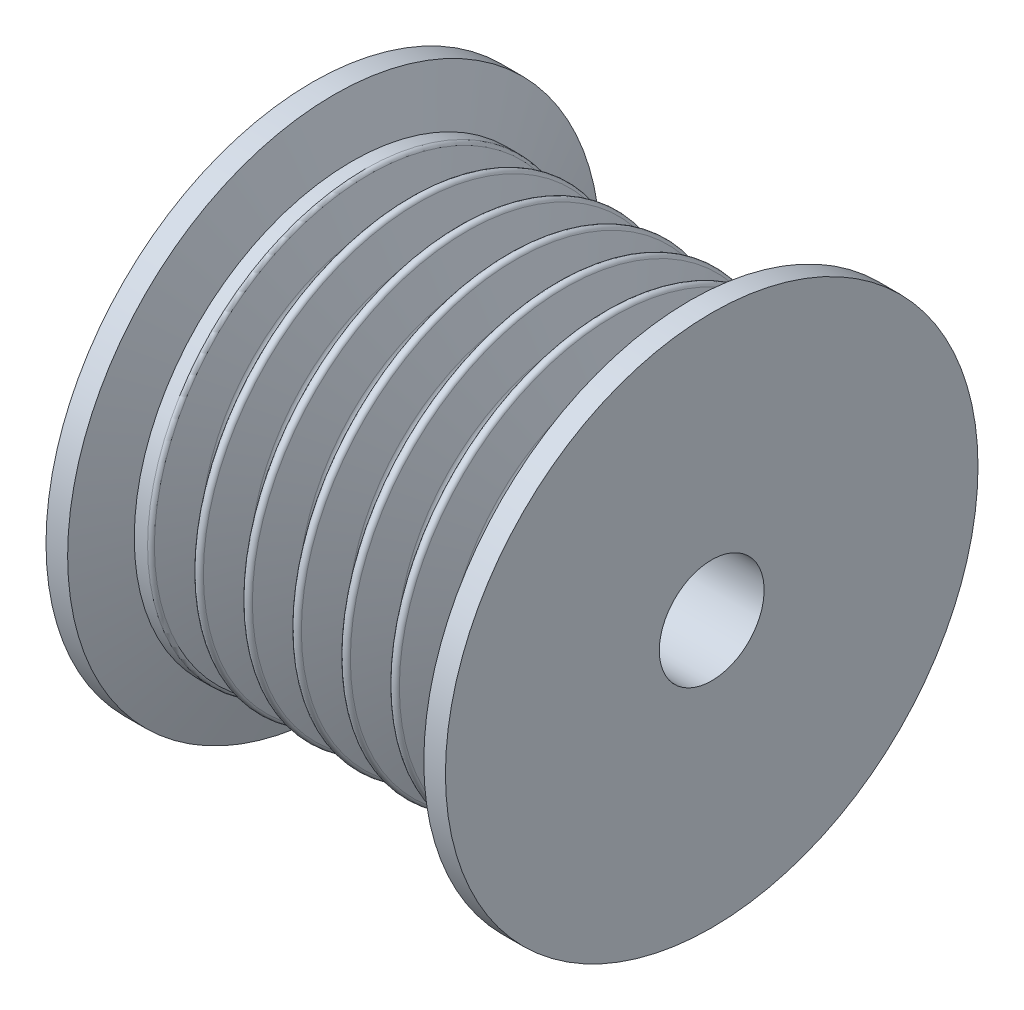
SolidWorks part; units mm, degrees
material "6061-T6 (SS)"
ref_plane "Front Plane" through (0, 0, 0) normal (0, 0, 1) x (1, 0, 0)
ref_plane "Top Plane" through (0, 0, 0) normal (0, 1, 0) x (1, 0, 0)
ref_plane "Right Plane" through (0, 0, 0) normal (1, 0, 0) x (0, 0, -1)
sketch "Sketch1" plane through (0, 0, 0) normal (0, 0, 1) x (1, 0, 0)
  line L0 (0, 0) -> (0, 2.5) construction
  line L1 (0, 2.5) -> (19.05, 2.5)
  line L2 (19.05, 2.5) -> (19.05, 12.7)
  line L3 (19.05, 12.7) -> (0, 12.7)
  line L4 (0, 12.7) -> (0, 2.5)
  line L5 (0, 0) -> (13.5959, 0) construction
  dimension "D1" = 25.4
  dimension "D2" = 5
  dimension "D3" = 19.05
revolve "Revolve1" add sketch "Sketch1" angle 360 about L5
sketch "Sketch2" plane through (0, 0, 0) normal (0, 0, 1) x (1, 0, 0)
  line L0 (14.1986, 12.7) -> (14.1986, 10.3699)
  line L2 (14.3895, 10.2362) -> (14.9851, 8.5999)
  line L3 (15.7489, 8.5999) -> (16.3445, 10.2362)
  line L4 (16.5354, 10.3699) -> (16.5354, 12.7)
  line L5 (16.5354, 12.7) -> (14.1986, 12.7)
  line L6 (14.1986, 11.43) -> (16.5354, 11.43) construction
  line L7 (0, 0) -> (24.4755, 0) construction
  line L8 (14.3895, 10.2362) -> (16.3445, 10.2362) construction
  line L9 (14.1986, 12.7) -> (11.8618, 12.7) construction
  line L10 (19.05, 12.7) -> (0, 12.7) construction
  line L11 (11.8618, 12.7) -> (9.525, 12.7) construction
  arc A0 (14.1986, 10.3699) -> (14.3895, 10.2362) centre (14.1986, 10.1667) cw
  arc A1 (14.9851, 8.5999) -> (15.7489, 8.5999) centre (15.367, 8.7389) ccw
  arc A2 (16.3445, 10.2362) -> (16.5354, 10.3699) centre (16.5354, 10.1667) cw
  dimension "D1" = 0.4064
  dimension "D5" = 0.2032
  dimension "D2" = 2.3368
  dimension "D3" = 11.43
  dimension "D4" = 1.1938
  dimension "D6" = 40
revolve "Cut-Revolve1" cut sketch "Sketch2" angle 360 about L7
pattern_linear "LPattern1" count 6 spacing 2.3368 along (-1, 0, 0) of "Cut-Revolve1"
sketch "Sketch3" plane through (0, 0, 0) normal (0, 0, 1) x (1, 0, 0)
  line L0 (16.5354, 12.7) -> (18.0185, 12.7)
  line L1 (19.05, 12.7) -> (16.5354, 12.7) construction
  line L2 (18.0185, 12.7) -> (17.1704, 10.3699)
  line L3 (17.1704, 10.3699) -> (16.5354, 10.3699)
  line L4 (16.5354, 12.7) -> (16.5354, -12.7) construction
  line L5 (16.5354, 10.3699) -> (16.5354, 12.7)
  line L6 (16.5354, 10.3699) -> (16.5354, -10.3699) construction
  line L7 (15.367, 8.3325) -> (15.367, 11.4458) construction
  line L8 (9.525, 10.3699) -> (9.525, 14.7012) construction
  line L9 (2.5146, 10.3699) -> (2.5146, 12.7)
  line L10 (1.8796, 10.3699) -> (2.5146, 10.3699)
  line L11 (1.0315, 12.7) -> (1.8796, 10.3699)
  line L12 (2.5146, 12.7) -> (1.0315, 12.7)
  line L13 (0, 0) -> (26.9583, 0) construction
  arc A0 (14.9851, 8.5999) -> (15.7489, 8.5999) centre (15.367, 8.7389) ccw construction
  arc A1 (9.7159, 10.2362) -> (9.3341, 10.2362) centre (9.525, 10.1667) ccw construction
  dimension "D1" = 1.8034
  dimension "D2" = 20
revolve "Cut-Revolve2" cut sketch "Sketch3" angle 360 about L13
equation "\"D2@Sketch1\"=5mm"
equation "\"D3@Sketch2\"=0.9in/2"
equation "\"D4@Sketch2\"=0.094in/2"
